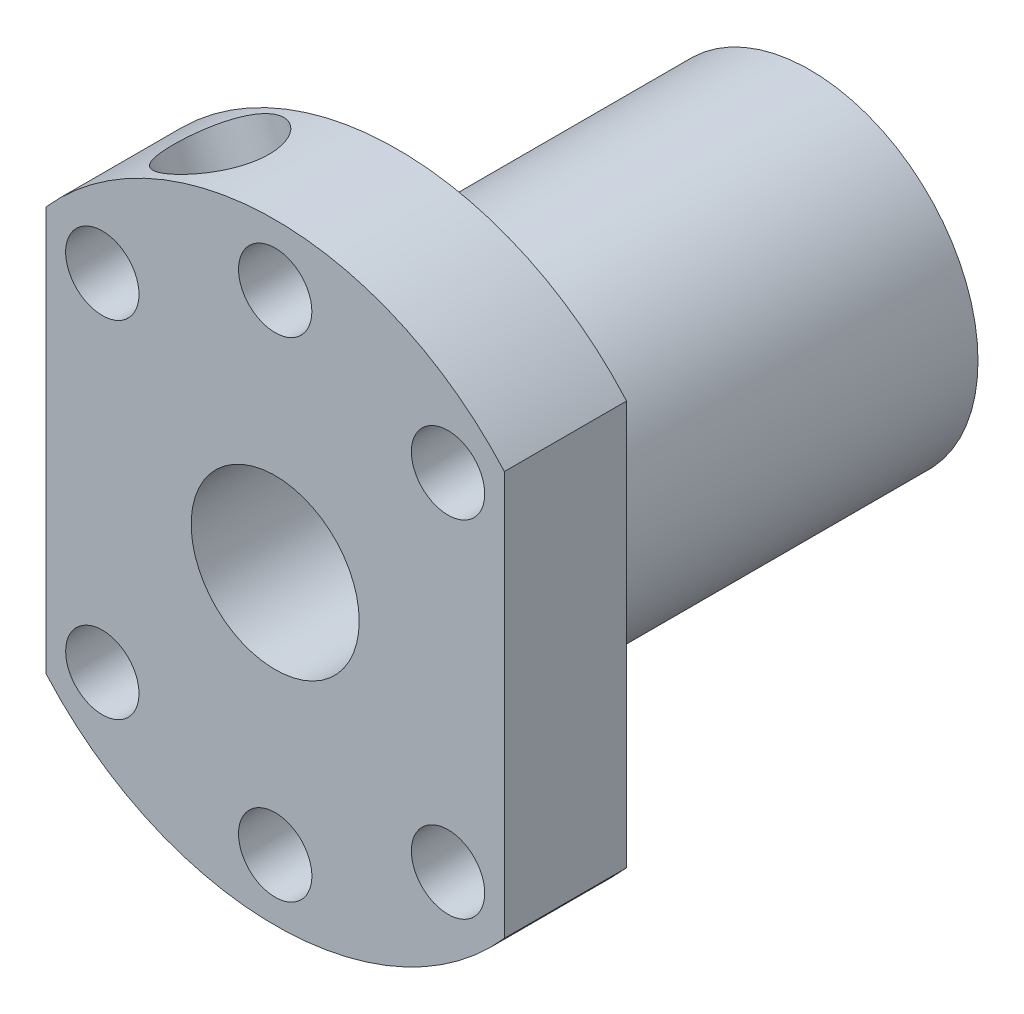
SolidWorks part; units mm, degrees
ref_plane "Front Plane" through (0, 0, 0) normal (0, 0, 1) x (1, 0, 0)
ref_plane "Top Plane" through (0, 0, 0) normal (0, 1, 0) x (1, 0, 0)
ref_plane "Right Plane" through (0, 0, 0) normal (1, 0, 0) x (0, 0, -1)
sketch "Sketch1" plane through (0, 0, 0) normal (0, 0, 1) x (1, 0, 0)
  line L0 (0, -20) -> (0, 20) construction
  line L1 (0, 0) -> (-15, 0) construction
  line L2 (-15, 13.2288) -> (-15, -13.2288)
  line L3 (15, 13.2288) -> (15, -13.2288)
  line L4 (0, 0) -> (-11.3137, 11.3137) construction
  line L5 (0, 0) -> (-7.6537, 18.4776) construction
  circle A0 centre (0, 0) radius 5.5
  circle A1 centre (-11.3137, 11.3137) radius 2.4
  circle A2 centre (0, 16) radius 2.4
  arc A5 (0, 16) -> (-11.3137, 11.3137) centre (0, 0) ccw construction
  arc A6 (15, 13.2288) -> (-15, 13.2288) centre (0, 0) ccw
  circle A8 centre (11.3137, 11.3137) radius 2.4
  circle A9 centre (11.3137, -11.3137) radius 2.4
  arc A10 (15, -13.2288) -> (-15, -13.2288) centre (0, 0) cw
  circle A11 centre (0, -16) radius 2.4
  circle A12 centre (-11.3137, -11.3137) radius 2.4
  point P12 (0, 0)
  point P29 (15, 0)
  dimension "D2" = 32
  dimension "D3" = 4.8
  dimension "D1" = 40
  dimension "D7" = 11
  dimension "D4" = 45
  dimension "D5" = 30
  dimension "D6" = 22.5
extrude "Boss-Extrude1" add sketch "Sketch1" against normal mid plane 8
sketch "Sketch2" plane through (0, 0, -4) normal (0, 0, -1) x (-1, 0, 0)
  circle A0 centre (0, 0) radius 11
  circle A1 centre (0, 0) radius 5.5 construction
  circle A2 centre (0, 0) radius 5.5
  dimension "D1" = 22
extrude "Boss-Extrude2" add sketch "Sketch2" along normal offset from surface (27 mm away) 35 up to face at (-13.7137, -11.3137, 4)
hole_wizard "M8x1.25 Tapped Hole1" positions "3DSketch3" profile "Sketch4" tap size "M8x1.25" standard "ANSI Metric"
sketch3d "3DSketch3"
  point P0 (-7.6537, 18.4776, 0)
  point P3 (-7.6537, 18.4776, 0)
  point P5 (-7.6537, 18.4776, 0)
sketch "Sketch4" plane through (-7.6537, 18.4776, 0) normal (0, 0, 1) x (-0.9239, -0.3827, 0)
  line L0 (0, 0) -> (0, 10.0429)
  line L1 (0, 10.0429) -> (3.4, 8)
  line L2 (3.4, 8) -> (3.4, 0)
  line L5 (3.4, 0) -> (0, 0)
  line L10 (0, 10.0429) -> (-3.4, 8) construction
  line L11 (0, -6.35) -> (0, 107.95) construction
  dimension "Tap Drill Dia." = 6.8
  dimension "Tap Drill Depth" = 8
  dimension "Drill Angle" = 118
cosmetic thread "Hole Thread3" parameters "D1"=8, "D2"=8
